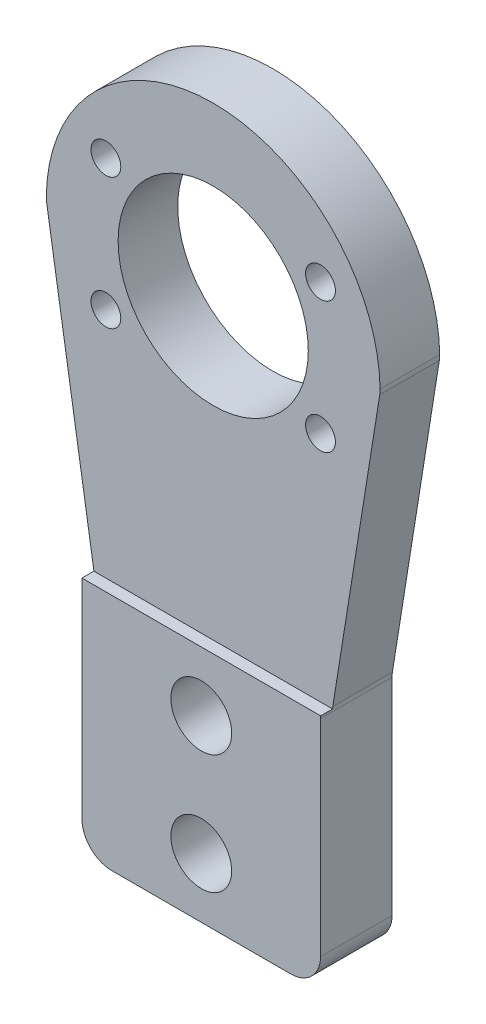
SolidWorks part; units mm, degrees
ref_plane "Front Plane" through (0, 0, 0) normal (0, 0, 1) x (1, 0, 0)
ref_plane "Top Plane" through (0, 0, 0) normal (0, 1, 0) x (1, 0, 0)
ref_plane "Right Plane" through (0, 0, 0) normal (1, 0, 0) x (0, 0, -1)
sketch "Sketch1" plane through (0, 0, 0) normal (0, 0, 1) x (1, 0, 0)
  line L0 (0, -353.8104) -> (0, 17336.7087) construction
  line L1 (-10, -15) -> (-10, 5)
  line L2 (-10, 5) -> (-14, 30)
  line L3 (10, -15) -> (-10, -15)
  line L4 (10, -15) -> (10, 5)
  line L5 (10, 5) -> (14, 30)
  arc A0 (14, 30) -> (-14, 30) centre (0, 30) ccw
  circle A1 centre (0, 0) radius 2.55
  circle A2 centre (0, -10) radius 2.55
  dimension "D1" = 5.1
  dimension "D2" = 5.1
  dimension "D3" = 10
  dimension "D4" = 28
  dimension "D5" = 30
  dimension "D7" = 20
  dimension "D6" = 5
  dimension "D8" = 20
  dimension "D9" = 10
  dimension "D10" = 20
extrude "Boss-Extrude2" add sketch "Sketch1" along normal blind 6
fillet "Fillet1" radius 2.5 6 edges at (-14, 30, 3) (14, 30, 3) (10, 5, 3) (10, -15, 3) (-10, -15, 3) (-10, 5, 3)
sketch "Sketch3" plane through (0, 0, 6) normal (0, 0, 1) x (1, 0, 0)
  circle A0 centre (0, 30) radius 7.975
  dimension "D1" = 15.95
extrude "Cut-Extrude2" cut sketch "Sketch3" against normal through all
sketch "Sketch2" plane through (0, 0, 6) normal (0, 0, 1) x (1, 0, 0)
  line L1 (-9, 24.5) -> (9, 24.5) construction
  line L2 (-9, 24.5) -> (-9, 35.5) construction
  line L3 (-9, 35.5) -> (9, 35.5) construction
  line L4 (9, 24.5) -> (9, 35.5) construction
  line L5 (-9, 24.5) -> (9, 35.5) construction
  line L6 (-9, 35.5) -> (9, 24.5) construction
  circle A0 centre (-9, 24.5) radius 1.25
  circle A1 centre (9, 24.5) radius 1.25
  circle A2 centre (-9, 35.5) radius 1.25
  circle A3 centre (9, 35.5) radius 1.25
  circle A5 centre (0, 30) radius 7.975 construction
  point P0 (0, 30)
  dimension "D3" = 2.5
  dimension "D4" = 2.5
  dimension "D5" = 2.5
  dimension "D6" = 2.5
  dimension "D1" = 18
  dimension "D2" = 11
extrude "Cut-Extrude1" cut sketch "Sketch2" against normal through all
sketch "Sketch6" plane through (0, 0, 6) normal (0, 0, 1) x (1, 0, 0)
  line L0 (-7.5, -15) -> (7.5, -15) construction
  line L1 (-20, 5) -> (20, 5)
  line L2 (-20, 5) -> (-20, 55)
  line L3 (-20, 55) -> (20, 55)
  line L4 (20, 5) -> (20, 55)
  line L5 (-20, 5) -> (20, 55) construction
  line L6 (-20, 55) -> (20, 5) construction
  point P0 (0, 30)
  dimension "D1" = 20
  dimension "D2" = 40
extrude "Cut-Extrude5" cut sketch "Sketch6" against normal blind 1
